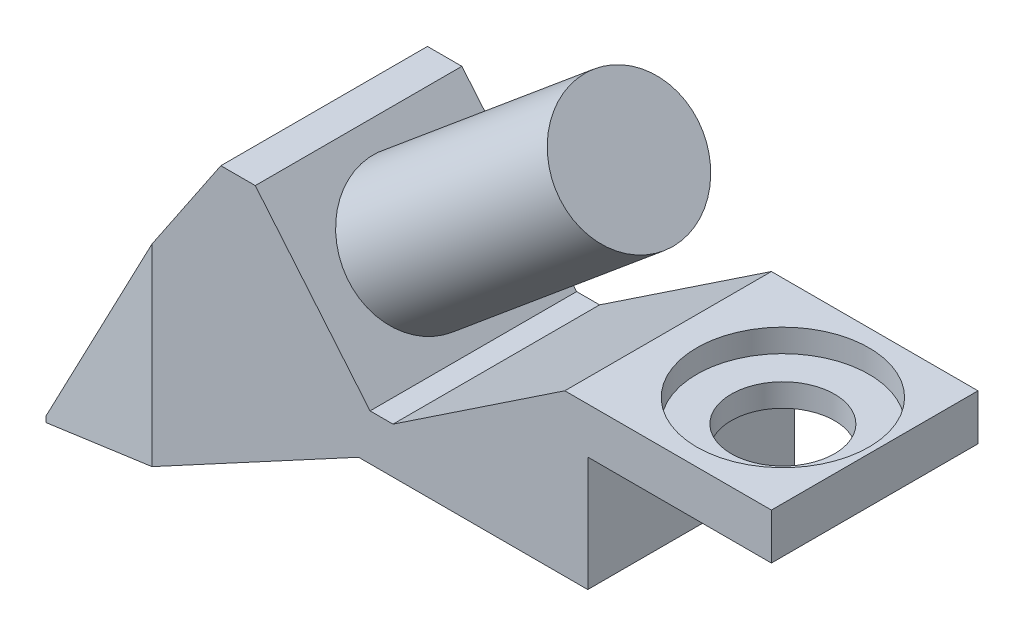
SolidWorks part; units mm, degrees
ref_plane "Front Plane" through (0, 0, 0) normal (0, 0, 1) x (1, 0, 0)
ref_plane "Top Plane" through (0, 0, 0) normal (0, 1, 0) x (1, 0, 0)
ref_plane "Right Plane" through (0, 0, 0) normal (1, 0, 0) x (0, 0, -1)
sketch "Sketch1" plane through (0, 0, 0) normal (0, 0, 1) x (1, 0, 0)
  line L0 (0, 0) -> (17.6167, 9.5)
  line L1 (17.6167, 9.5) -> (27.6, 9.5)
  line L2 (27.6, 9.5) -> (27.6, 14.5)
  line L3 (27.6, 14.5) -> (35.6, 14.5)
  line L4 (35.6, 14.5) -> (35.6, 16.5)
  line L5 (35.6, 16.5) -> (26.6, 16.5)
  line L8 (11.6167, 17.5) -> (0, 0.25)
  line L10 (18.1167, 11.5) -> (13.1167, 17.5)
  line L11 (13.1167, 17.5) -> (11.6167, 17.5)
  line L12 (26.6, 16.5) -> (19.1167, 11.5)
  line L13 (19.1167, 11.5) -> (18.1167, 11.5)
  line L14 (0, 0) -> (0, 0.25)
  dimension "D1" = 35.6
  dimension "D2" = 9.5
  dimension "D3" = 14.5
  dimension "D4" = 17.5
  dimension "D5" = 2
  dimension "D6" = 8
  dimension "D7" = 2
  dimension "D8" = 1.5
  dimension "D9" = 0.5
  dimension "D10" = 1
  dimension "D11" = 1
  dimension "D12" = 5
  dimension "D13" = 9
  dimension "D14" = 0.25
extrude "Boss-Extrude1" add sketch "Sketch1" along normal blind 9
sketch "Sketch2" plane through (0, 16.5, 0) normal (0, 1, 0) x (1, 0, 0)
  line L0 (35.6, -9) -> (35.6, 0) construction
  line L1 (8.6167, 0) -> (0, 0)
  line L2 (0, 0) -> (0, -4)
  line L3 (0, -4) -> (8.6167, 0)
  line L4 (0, -5) -> (0, -9)
  line L5 (0, -9) -> (8.6167, -9)
  line L6 (0, -9) -> (0, 0) construction
  line L7 (11.6167, 0) -> (0, 0) construction
  line L8 (0, -5) -> (8.6167, -9)
  line L9 (11.6167, -9) -> (0, -9) construction
  line L10 (11.6167, -9) -> (11.6167, 0) construction
  circle A0 centre (31.6, -4.5) radius 2.25
  circle A1 centre (31.6, -4.5) radius 3.75
  point P5 (35.6, -4.5)
  point P19 (0, -4.5)
  dimension "D3" = 4.5
  dimension "D5" = 7.5
  dimension "D1" = 4
  dimension "D2" = 1
  dimension "D4" = 3
  dimension "D6" = 0.5
extrude "Cut-Extrude1" cut sketch "Sketch2" against normal up to vertex (16.5 mm away) contours A0 | L2 L3 L1 | L8 L4 L5 region at (2.8722, 16.5, 1.3333) region at (2.8722, 16.5, 7.6667) region at (31.6, 16.5, 4.5) up to point (0, 0, 9)
extrude "Cut-Extrude2" cut sketch "Sketch2<3>" against normal blind 1 contours A1 A0 region at (27.9561, 16.5, 4.5)
sketch "Sketch2<3>" plane through (0, 16.5, 0) normal (0, 1, 0) x (1, 0, 0) same geometry as "Sketch2"
sketch "Sketch3" plane through (16.3476, 13.623, 0) normal (0.7682, 0.6402, 0) x (0, 0, -1)
  line L0 (-9, 5.0468) -> (0, 5.0468) construction
  circle A0 centre (-4.5, 1.0468) radius 3
  point P4 (-4.5, 5.0468)
  dimension "D1" = 6
  dimension "D2" = 4
extrude "Boss-Extrude2" add sketch "Sketch3" along normal blind 12
equation "\"D6@Sketch2\"=\"D2@Sketch2\"/2"
